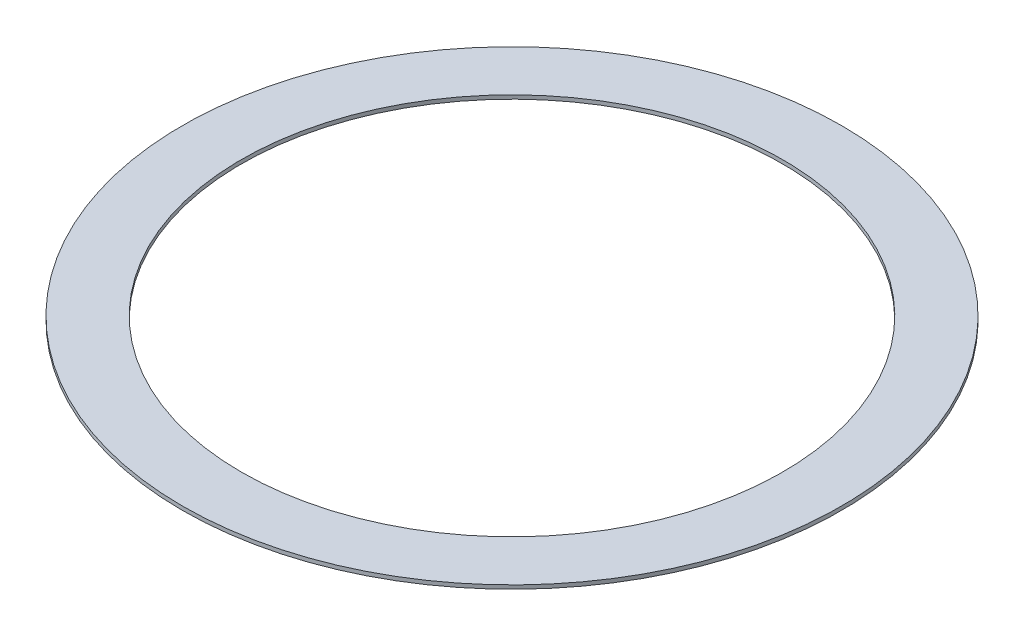
SolidWorks part; units mm, degrees
ref_plane "Front Plane" through (0, 0, 0) normal (0, 0, 1) x (1, 0, 0)
ref_plane "Top Plane" through (0, 0, 0) normal (0, 1, 0) x (1, 0, 0)
ref_plane "Right Plane" through (0, 0, 0) normal (1, 0, 0) x (0, 0, -1)
sketch "Sketch1" plane through (0, 0, 0) normal (0, 1, 0) x (1, 0, 0)
  circle A0 centre (0, 0) radius 357.2792
  circle A1 centre (0, 0) radius 435
  dimension "D1" = 714.5584
  dimension "D2" = 870
extrude "Boss-Extrude1" add sketch "Sketch1" along normal blind 5
